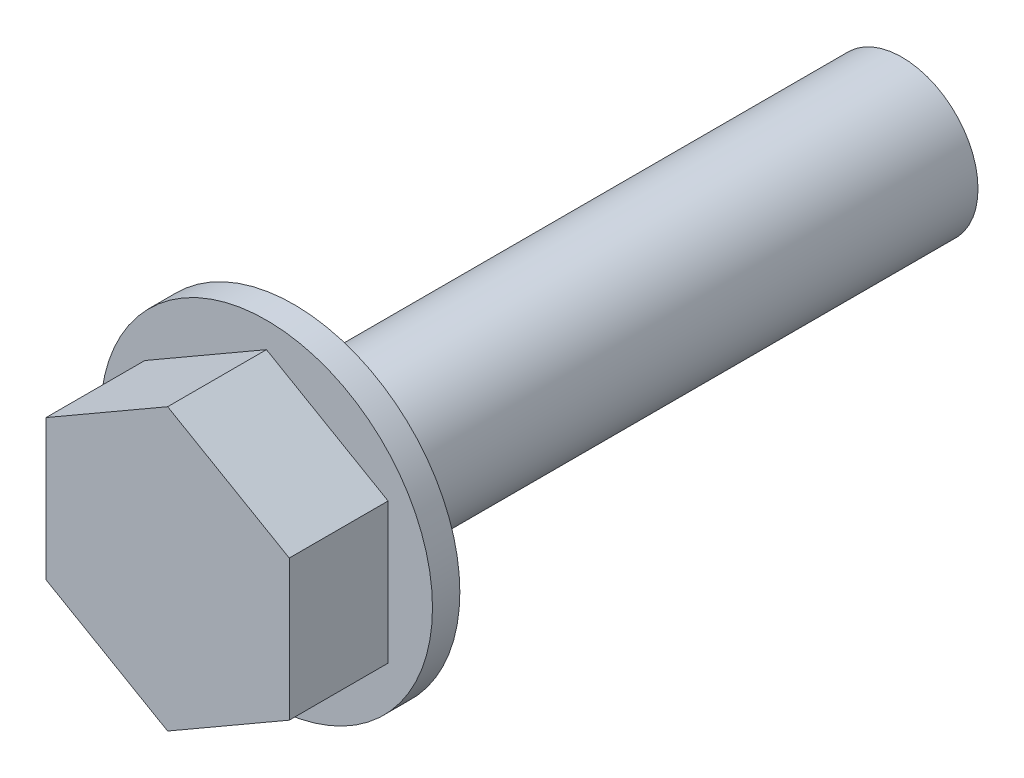
SolidWorks part; units mm, degrees
material "AISI Type 316L stainless steel"
ref_plane "Front Plane" through (0, 0, 0) normal (0, 0, 1) x (1, 0, 0)
ref_plane "Top Plane" through (0, 0, 0) normal (0, 1, 0) x (1, 0, 0)
ref_plane "Right Plane" through (0, 0, 0) normal (1, 0, 0) x (0, 0, -1)
sketch "Extrude sketch 1" plane through (0, 0, 0) normal (0, 0, 1) x (1, 0, 0)
  circle A0 centre (0, 0) radius 10.92
  dimension "D1" = 21.84
extrude "Extrude 1" add sketch "Extrude sketch 1" along normal blind 1.8 separate body
sketch "Extrude sketch 2" plane through (0, 0, 0) normal (0, 0, 1) x (1, 0, 0)
  line L0 (8, 4.6188) -> (0, 9.2376)
  line L1 (0, 9.2376) -> (-8, 4.6188)
  line L2 (-8, 4.6188) -> (-8, -4.6188)
  line L3 (-8, -4.6188) -> (0, -9.2376)
  line L4 (0, -9.2376) -> (8, -4.6188)
  line L5 (8, -4.6188) -> (8, 4.6188)
  dimension "D1" = 8
  dimension "D2" = 4.6188
extrude "Extrude 2" add sketch "Extrude sketch 2" along normal blind 6.5 from offset 1.8 separate body
sketch "Extrude sketch 3" plane through (0, 0, 0) normal (0, 0, 1) x (1, 0, 0)
  circle A0 centre (0, 0) radius 5
  dimension "D1" = 10
extrude "Extrude 3" add sketch "Extrude sketch 3" along normal blind 40.01 from offset 40 separate body offset against normal yes
combine bodies "Combine (weld / assembly of features)" operation type add bodies to combine 103 102 101
